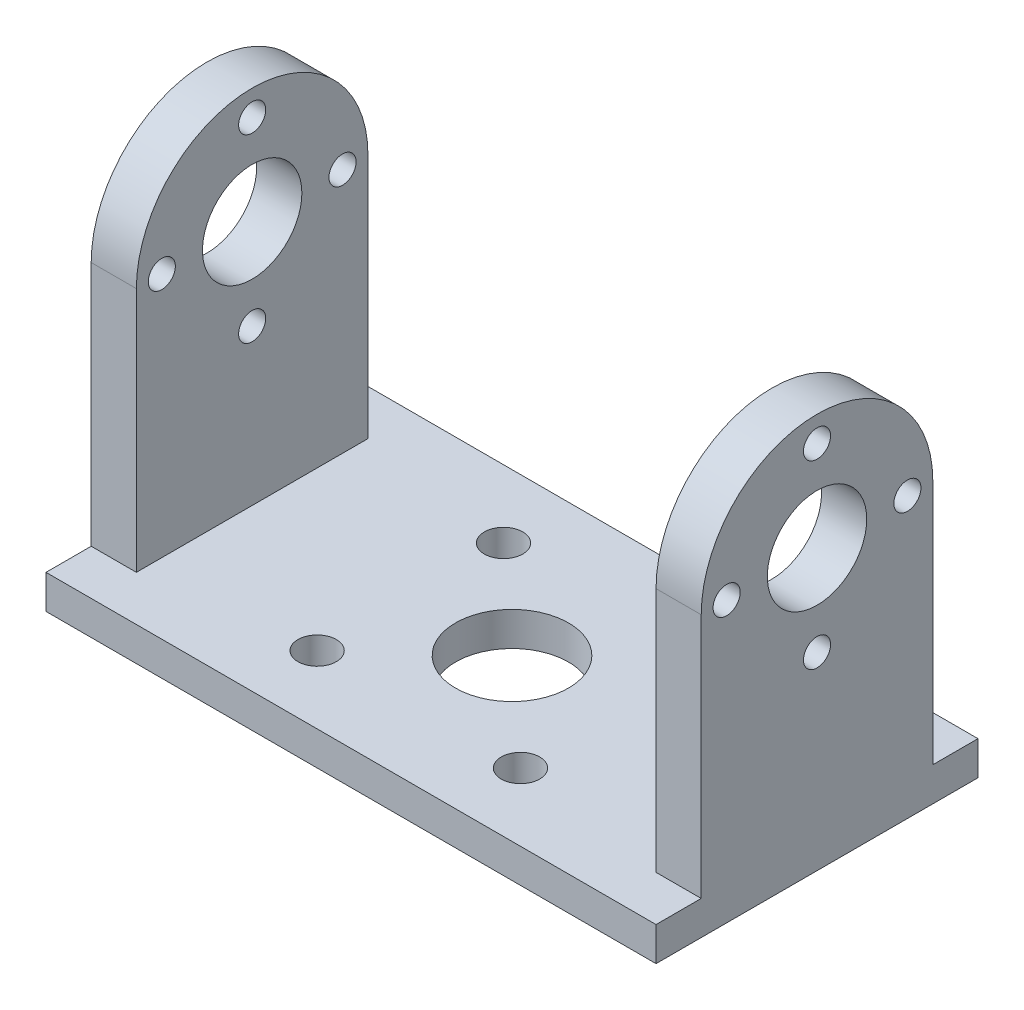
SolidWorks part; units mm, degrees
ref_plane "Front Plane" through (0, 0, 0) normal (0, 0, 1) x (1, 0, 0)
ref_plane "Top Plane" through (0, 0, 0) normal (0, 1, 0) x (1, 0, 0)
ref_plane "Right Plane" through (0, 0, 0) normal (1, 0, 0) x (0, 0, -1)
sketch "Sketch1" plane through (0, 0, 0) normal (0, 1, 0) x (1, 0, 0)
  line L0 (0, 0) -> (0, -7.6155) construction
  line L1 (-18, 14.25) -> (18, 14.25)
  line L2 (-18, 14.25) -> (-18, -14.25)
  line L3 (-18, -14.25) -> (18, -14.25)
  line L4 (18, 14.25) -> (18, -14.25)
  line L6 (-18, 14.25) -> (-27, 14.25)
  line L7 (-18, 14.25) -> (-18, -14.25)
  line L8 (-18, -14.25) -> (-27, -14.25)
  line L9 (-27, 14.25) -> (-27, -14.25)
  line L10 (18, 14.25) -> (27, 14.25)
  line L11 (18, 14.25) -> (18, -14.25)
  line L12 (18, -14.25) -> (27, -14.25)
  line L13 (27, 14.25) -> (27, -14.25)
  circle A0 centre (0, 0) radius 5
  circle A1 centre (-9, 8.25) radius 1.7
  circle A2 centre (-9, -8.25) radius 1.7
  circle A3 centre (9, -8.25) radius 1.7
  circle A4 centre (9, 8.25) radius 1.7
  point P0 (0, 0)
  dimension "D3" = 9
  dimension "D4" = 8.25
  dimension "D5" = 8.25
  dimension "D6" = 9
  dimension "D7" = 9
  dimension "D1" = 36
  dimension "D2" = 28.5
  dimension "D8" = 9
extrude "Boss-Extrude2" add sketch "Sketch1" along normal blind 3 contours L6 L9 L8 L2 | L13 L10 L4 L12 | L4 L1 L2 L3 A3 A2 A1 A0 A4 region at (0, 0, -13.7908) region at (-22.5, 0, 0) region at (22.5, 0, 0)
sketch "Sketch2" plane through (0, 3, 0) normal (0, 1, 0) x (1, 0, 0)
  line L5 (27, 14.25) -> (27, -14.25) construction
  line L6 (27, 10.25) -> (23, 10.25)
  line L7 (27, 10.25) -> (27, -10.25)
  line L8 (27, -10.25) -> (23, -10.25)
  line L9 (23, 10.25) -> (23, -10.25)
  line L10 (27, 14.25) -> (-27, 14.25) construction
  dimension "D1" = 4
  dimension "D2" = 20.5
  dimension "D3" = 4
extrude "Boss-Extrude3" add sketch "Sketch2" along normal blind 21.75
sketch "Sketch4" plane through (27, 0, 0) normal (1, 0, 0) x (0, 0, -1)
  line L0 (-10.25, 24.75) -> (10.25, 24.75) construction
  circle A0 centre (0, 24.75) radius 10.25
  point P18 (0, 17.75)
  line M5 (10.25, 24.75) -> (-10.25, 24.75)
extrude "Boss-Extrude4" add sketch "Sketch4" against normal blind 4 contours A0 M5 | M5 | M5 | A0 M5 region at (27, 29.1002, 0) region at (27, 20.3998, 0)
ref_plane "Plane1" through (0, 0, 0) normal (1, 0, 0) x (0, 0, -1)
mirror "Mirror1" about plane through (0, 0, 0) normal (1, 0, 0) of "Boss-Extrude3", "Boss-Extrude4"
sketch "Sketch6" plane through (27, 0, 0) normal (1, 0, 0) x (0, 0, -1)
  line L0 (-10.25, 24.75) -> (10.25, 24.75) construction
  line L1 (0, 35) -> (0, 14.5) construction
  circle A6 centre (0, 24.75) radius 4.4
  circle A7 centre (0, 24.75) radius 8
  circle A8 centre (0, 32.75) radius 1.2
  circle A9 centre (8, 24.75) radius 1.2
  circle A10 centre (0, 16.75) radius 1.2
  circle A11 centre (-8, 24.75) radius 1.2
  circle A12 centre (0, 24.75) radius 10.25
  point P21 (0, 24.75)
  dimension "D1" = 8.8
  dimension "D2" = 16
  dimension "D3" = 4
  dimension "D4" = 2.4
extrude "Cut-Extrude3" cut sketch "Sketch6" against normal blind 4 contours A6 | A7 A11 | A7 A11 | A7 A10 | A7 A10 | A7 A9 | A7 A9 | A7 A8 | A7 A8 region at (27, 24.75, 0) region at (27, 24.75, -7.4748) region at (27, 24.75, -8.4927) region at (27, 32.2248, 0) region at (27, 33.2427, 0) region at (27, 16.2573, 0) region at (27, 17.2752, 0) region at (27, 24.75, 7.4748) region at (27, 24.75, 8.4927)
mirror "Mirror3" about plane through (0, 0, 0) normal (1, 0, 0) of "Cut-Extrude3"
